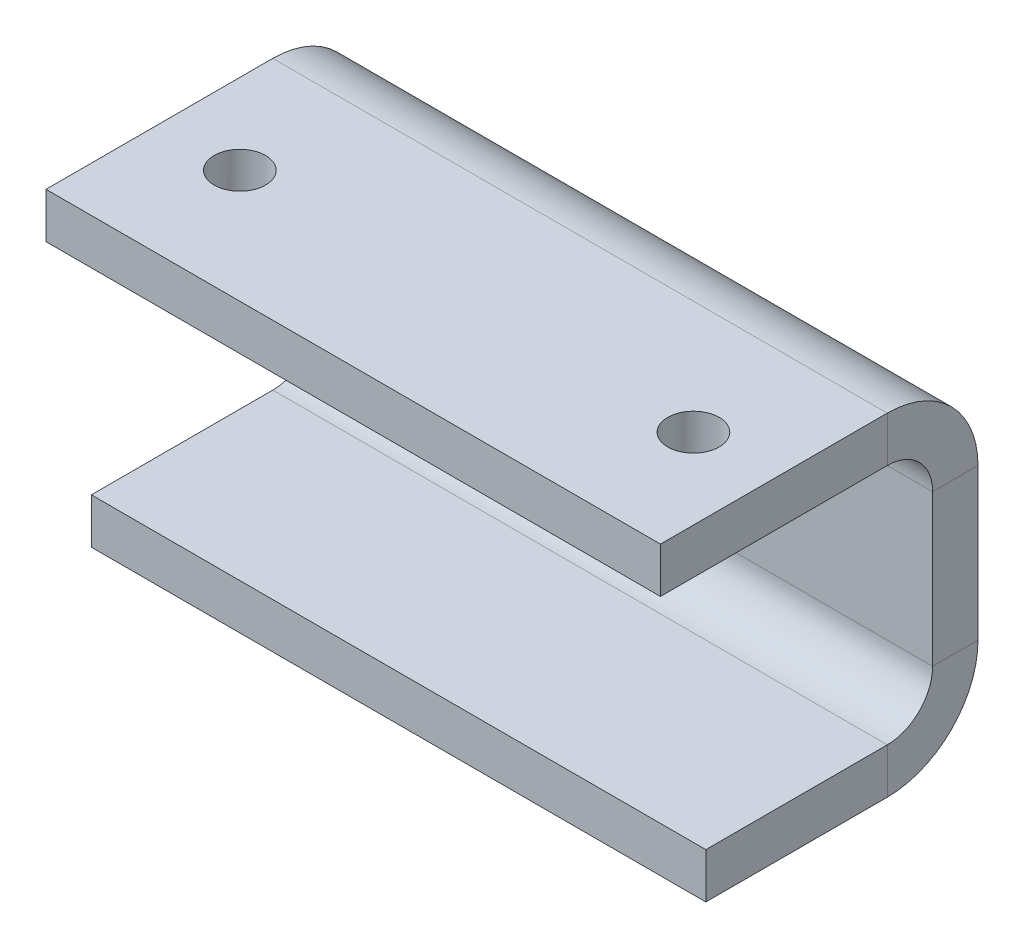
SolidWorks part; units mm, degrees
note: The reader was unsure of these and kept them because the rebuilt part matched: flange length of "Edge-Flange1", "Edge-Flange2".
material "6061 Alloy"
ref_plane "Front Plane" through (0, 0, 0) normal (0, 0, 1) x (1, 0, 0)
ref_plane "Top Plane" through (0, 0, 0) normal (0, 1, 0) x (1, 0, 0)
ref_plane "Right Plane" through (0, 0, 0) normal (1, 0, 0) x (0, 0, -1)
sketch "Sketch2" plane through (0, 0, 0) normal (0, 1, 0) x (1, 0, 0)
  line L1 (-20.32, -7.5) -> (20.32, -7.5)
  line L2 (-20.32, -7.5) -> (-20.32, 7.5)
  line L3 (-20.32, 7.5) -> (20.32, 7.5)
  line L4 (20.32, -7.5) -> (20.32, 7.5)
  line L5 (-20.32, -7.5) -> (20.32, 7.5) construction
  line L6 (-20.32, 7.5) -> (20.32, -7.5) construction
  point P0 (0, 0)
  dimension "D1" = 15
  dimension "D2" = 40.64
base flange "Base-Flange1" sketch "Sketch2" thickness 3 reverse thickness direction no parameters "D1"=3
edge flange "Edge-Flange1" sketch "Sketch9" flange angle 90 flange length 13 flange position bend outside bend radius 3 thickness 3 relief rectangular parameters "D6"=10
sketch "Sketch9" plane through (0, -3, -7.5) normal (0, 0, 1) x (-1, 0, 0)
  line L1 (20.32, 0) -> (-20.32, 0) construction
  line L2 (-20.32, 0) -> (-20.32, 13)
  line L3 (-20.32, 13) -> (20.32, 13)
  line L4 (20.32, 13) -> (20.32, 0)
  line L5 (20.32, 0) -> (-20.32, 0)
bend "EdgeBend1" bend radius 3 bend angle 90 parameters "D5"=1
edge flange "Edge-Flange2" sketch "Sketch12" flange angle 90 flange length 15 flange position bend outside bend radius 3 thickness 3 relief rectangular parameters "D6"=10
sketch "Sketch12" plane through (0, -16, -10.5) normal (0, -1, 0) x (1, 0, 0)
  line L2 (-20.32, 0) -> (-20.32, 15)
  line L3 (-20.32, 15) -> (20.32, 15)
  line L4 (20.32, 15) -> (20.32, 0)
  line L5 (-20.32, 0) -> (20.32, 0) construction
  line L6 (-20.32, 0) -> (20.32, 0)
bend "EdgeBend2" bend radius 3 bend angle 90 parameters "D5"=2
hole_wizard "M3 Clearance Hole1" positions "Sketch15" profile "Sketch16" hole size "M3" standard "ANSI Metric" end condition up to next
sketch "Sketch15" plane through (0, 0, 0) normal (0, 1, 0) x (1, 0, 0)
  line L0 (0, -7.5) -> (0, 7.5) construction
  line L1 (-20.32, -7.5) -> (20.32, -7.5) construction
  line L2 (20.32, 7.5) -> (-20.32, 7.5) construction
  point P0 (-15, 0)
  point P2 (15, 0)
  dimension "D1" = 15
  dimension "D2" = 15
sketch "Sketch16" plane through (-15, 0, 0) normal (1, 0, 0) x (0, 0, 1)
  line L0 (0, 0) -> (0, 3)
  line L1 (0, 3) -> (1.7, 3)
  line L2 (1.7, 3) -> (1.7, 0)
  line L5 (1.7, 0) -> (0, 0)
  line L11 (0, -6.35) -> (0, 107.95) construction
  dimension "Thru Hole Dia." = 3.4
  dimension "Thru Hole Depth" = 3
sketch "Bend-Lines1" [suppressed] plane through (0, 0, 0) normal (0, 1, 0) x (1, 0, 0)
sketch "Bounding-Box1" [suppressed] plane through (0, 0, 0) normal (0, 1, 0) x (1, 0, 0)
sheet metal parameters "Sheet-Metal5" thickness 3 parameters "D1"=3
flat pattern "Flat-Pattern5" [suppressed]
sketch "Bend-Lines2" plane through (0, 0, 0) normal (0, 1, 0) x (1, 0, 0)
sketch3d "Bounding-Box2" [suppressed]
  line L0 (17.5, -25.4, 0) -> (17.5, 25.4, 0) construction
  line L1 (-17.5, -25.4, 0) -> (-17.5, 25.4, 0) construction
  line L2 (17.5, -25.4, 0) -> (-17.5, -25.4, 0) construction
  line L3 (17.5, 25.4, 0) -> (-17.5, 25.4, 0) construction
sheet metal parameters "Sheet-Metal6" thickness 3 parameters "D1"=3
flat pattern "Flat-Pattern5"
sketch "Bend-Lines2" plane through (0, 0, 0) normal (0, 1, 0) x (1, 0, 0)
  line L0 (17.5, 11.0343) -> (-17.5, 11.0343) construction
  line L1 (17.5, 11.0343) -> (-17.5, 11.0343) construction
sketch3d "Bounding-Box2" [suppressed]
  line L0 (17.5, 24.5686, 0) -> (-17.5, 24.5686, 0) construction
  line L1 (17.5, -7.5, 0) -> (-17.5, -7.5, 0) construction
  line L2 (17.5, 24.5686, 0) -> (17.5, -7.5, 0) construction
  line L3 (-17.5, 24.5686, 0) -> (-17.5, -7.5, 0) construction
bend of the flat pattern "Flatten-<EdgeBend1>1"
sheet metal parameters "Sheet-Metal7" thickness 3 parameters "D1"=3
flat pattern "Flat-Pattern5"
sketch "Bend-Lines2" plane through (0, 0, 0) normal (0, 1, 0) x (1, 0, 0)
  line L0 (20.32, 11.0343) -> (-20.32, 11.0343) construction
  line L1 (20.32, 11.0343) -> (-20.32, 11.0343) construction
  line L2 (20.32, 28.1029) -> (-20.32, 28.1029) construction
  line L3 (20.32, 28.1029) -> (-20.32, 28.1029) construction
sketch3d "Bounding-Box2" [suppressed]
  line L0 (-20.32, -7.5, 0) -> (-20.32, 43.6372, 0) construction
  line L1 (20.32, -7.5, 0) -> (20.32, 43.6372, 0) construction
  line L2 (-20.32, -7.5, 0) -> (20.32, -7.5, 0) construction
  line L3 (-20.32, 43.6372, 0) -> (20.32, 43.6372, 0) construction
bend of the flat pattern "Flatten-<EdgeBend1>1"
bend of the flat pattern "Flatten-<EdgeBend2>1"
sheet metal parameters "Sheet-Metal8" thickness 3 parameters "D1"=3
flat pattern "Flat-Pattern5"
sketch "Bend-Lines2" plane through (0, 0, 0) normal (0, 1, 0) x (1, 0, 0)
  line L0 (20.32, 11.0343) -> (-20.32, 11.0343) construction
  line L1 (20.32, 11.0343) -> (-20.32, 11.0343) construction
  line L2 (20.32, 28.1029) -> (-20.32, 28.1029) construction
  line L3 (20.32, 28.1029) -> (-20.32, 28.1029) construction
sketch3d "Bounding-Box2" [suppressed]
  line L0 (-20.32, -7.5, 0) -> (-20.32, 43.6372, 0) construction
  line L1 (20.32, -7.5, 0) -> (20.32, 43.6372, 0) construction
  line L2 (-20.32, -7.5, 0) -> (20.32, -7.5, 0) construction
  line L3 (-20.32, 43.6372, 0) -> (20.32, 43.6372, 0) construction
bend of the flat pattern "Flatten-<EdgeBend1>1"
bend of the flat pattern "Flatten-<EdgeBend2>1"
